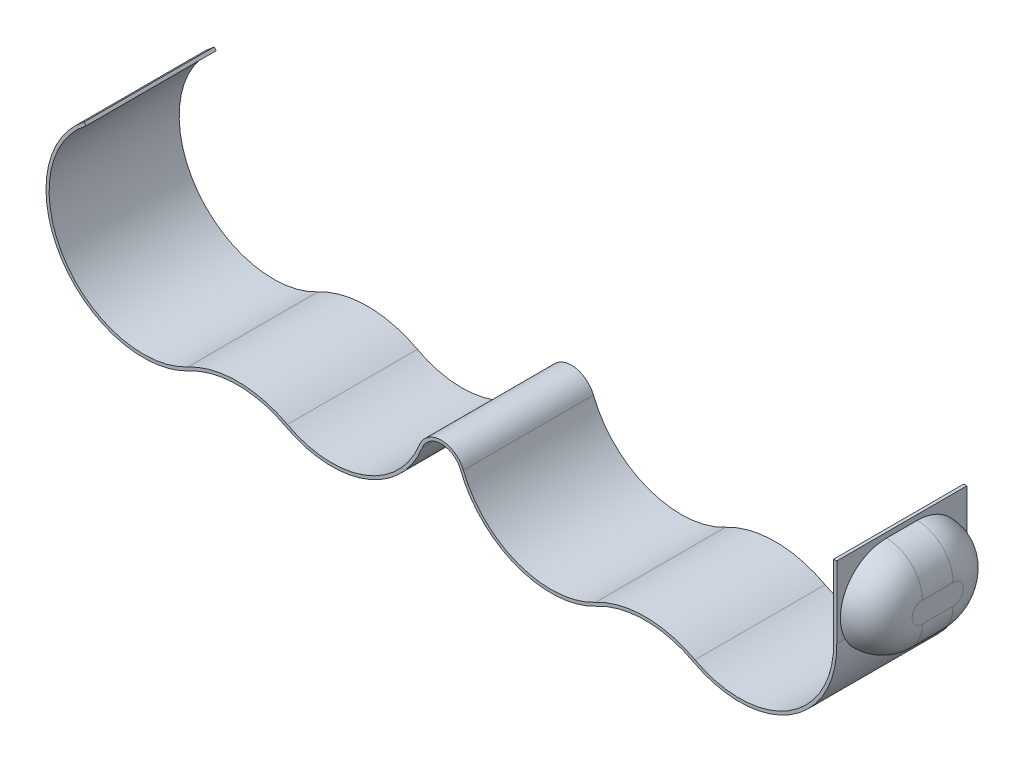
SolidWorks part; units mm, degrees
material "Kapton Film"
ref_plane "Front Plane" through (0, 0, 0) normal (0, 0, 1) x (1, 0, 0)
ref_plane "Top Plane" through (0, 0, 0) normal (0, 1, 0) x (1, 0, 0)
ref_plane "Right Plane" through (0, 0, 0) normal (1, 0, 0) x (0, 0, -1)
sketch "Battery Holder Outline" plane through (0, 0, 0) normal (0, 0, 1) x (1, 0, 0)
  line L0 (1.8682, 8) -> (-1.8682, 8) construction
  line L1 (-37.9318, 8) -> (-42.3, 8) construction
  line L2 (-42.3, 8) -> (-42.3, 0) construction
  line L3 (37.9318, 8) -> (42.3, 8) construction
  line L4 (42.3, 8) -> (42.3, 0) construction
  line L5 (42.3, 0) -> (-42.3, 0) construction
  arc A0 (-1.8682, 8) -> (-15.1821, 3.1238) centre (-10.7, 11.5) cw construction
  arc A1 (-24.6179, 3.1238) -> (-37.9318, 8) centre (-29.1, 11.5) cw construction
  arc A2 (24.6179, 3.1238) -> (37.9318, 8) centre (29.1, 11.5) ccw construction
  arc A3 (1.8682, 8) -> (15.1821, 3.1238) centre (10.7, 11.5) ccw construction
  arc A4 (24.6179, 3.1238) -> (15.1821, 3.1238) centre (19.9, -5.6933) ccw construction
  arc A5 (-15.1821, 3.1238) -> (-24.6179, 3.1238) centre (-19.9, -5.6933) ccw construction
  point P15 (0, 0)
  dimension "D1" = 9.5
  dimension "D2" = 10
  dimension "D3" = 84.6
  dimension "D4" = 8
  dimension "D5" = 3.7365
  dimension "D6" = 11.5
  dimension "D7" = 4.3682
sketch "Sketch2" plane through (0, 0, 0) normal (0, 0, 1) x (1, 0, 0)
  line L3 (-34.8747, 19.0434) -> (-34.6924, 18.8052)
  line L7 (38.5984, 11.6746) -> (38.5984, 18.6691)
  line L8 (38.5984, 18.6691) -> (38.2984, 18.6691)
  line L9 (38.2984, 18.6691) -> (38.2984, 11.6691)
  arc A0 (-15.1821, 3.1238) -> (-1.8682, 8) centre (-10.7, 11.5) ccw construction
  arc A1 (-15.1821, 3.1238) -> (-24.6179, 3.1238) centre (-19.9, -5.6933) ccw construction
  arc A2 (-37.9318, 8) -> (-24.6179, 3.1238) centre (-29.1, 11.5) ccw construction
  arc A3 (-15.1821, 3.1238) -> (-1.8682, 8) centre (-10.7, 11.5) ccw
  arc A4 (-15.1821, 3.1238) -> (-24.6179, 3.1238) centre (-19.9, -5.6933) ccw
  arc A5 (-37.9318, 8) -> (-24.6179, 3.1238) centre (-29.1, 11.5) ccw
  arc A13 (24.6179, 3.1238) -> (15.1821, 3.1238) centre (19.9, -5.6933) ccw construction
  arc A14 (1.8682, 8) -> (15.1821, 3.1238) centre (10.7, 11.5) ccw construction
  arc A15 (24.6179, 3.1238) -> (37.9318, 8) centre (29.1, 11.5) ccw construction
  arc A16 (24.6179, 3.1238) -> (38.5984, 11.6746) centre (29.1, 11.5) ccw
  arc A17 (24.6179, 3.1238) -> (15.1821, 3.1238) centre (19.9, -5.6933) ccw
  arc A18 (1.8682, 8) -> (15.1821, 3.1238) centre (10.7, 11.5) ccw
  arc A19 (-1.8682, 8) -> (1.8682, 8) centre (0, 7.2596) cw
  arc A21 (-37.9318, 8) -> (-34.8747, 19.0434) centre (-29.1, 11.5) cw
  arc A22 (-37.6529, 8.1105) -> (-34.6924, 18.8052) centre (-29.1, 11.5) cw
  arc A23 (-37.6529, 8.1105) -> (-24.7595, 3.3883) centre (-29.1, 11.5) ccw
  arc A24 (-15.0405, 3.3883) -> (-24.7595, 3.3883) centre (-19.9, -5.6933) ccw
  arc A25 (-15.0405, 3.3883) -> (-2.1471, 8.1105) centre (-10.7, 11.5) ccw
  arc A26 (-2.1471, 8.1105) -> (2.1471, 8.1105) centre (0, 7.2596) cw
  arc A27 (2.1471, 8.1105) -> (15.0405, 3.3883) centre (10.7, 11.5) ccw
  arc A28 (24.7595, 3.3883) -> (15.0405, 3.3883) centre (19.9, -5.6933) ccw
  arc A29 (24.7595, 3.3883) -> (38.2984, 11.6691) centre (29.1, 11.5) ccw
  arc A31 (38.5984, 11.6746) -> (37.4623, 16.008) centre (29.1, 11.5) ccw construction
  arc A32 (38.2984, 11.6691) -> (37.1982, 15.8656) centre (29.1, 11.5) ccw construction
  point P6 (37.9237, 15.0203)
  dimension "D1" = 0.3
  dimension "D4" = 7
  dimension "D2" = 19.1406
  dimension "D3" = 12.3
extrude "Boss-Extrude1" add sketch "Sketch2" along normal mid plane 12.7
ref_plane "Plane1" through (37.9237, 15.0203, 0) normal (0.9288, 0.3706, 0) x (0, 0, -1)
ref_plane "Plane2" through (42.5677, 16.8731, 0) normal (0.9288, 0.3706, 0) x (0, 0, -1)
sketch "Sketch6" plane through (38.5984, 16.1106, 0) normal (1, 0, 0) x (0, 0, -1)
  line L0 (-1.5, -2.4415) -> (1.5, -2.4415) construction
  line L1 (-1.5, 2.0585) -> (1.5, 2.0585)
  line L2 (-1.5, -6.9415) -> (1.5, -6.9415)
  line L3 (-6.35, 2.5585) -> (6.35, 2.5585) construction
  arc A0 (-1.5, 2.0585) -> (-1.5, -6.9415) centre (-1.5, -2.4415) ccw
  arc A1 (1.5, -6.9415) -> (1.5, 2.0585) centre (1.5, -2.4415) ccw
  point P2 (0, -2.4415)
  point P12 (0, 2.5585)
  point P14 (6, -2.4415)
  point P15 (-6, -2.4415)
  dimension "D1" = 12
  dimension "D3" = 0.5
  dimension "D2" = 9
extrude "Boss-Extrude3" add sketch "Sketch6" against normal up to next (0.2999 mm away) and the other way blind 3.51
sketch "Sketch5" plane through (0, 0, 6.35) normal (0, 0, 1) x (1, 0, 0)
  line L2 (36.9572, 21.8694) -> (47.6324, 21.8694)
  line L3 (47.6324, 21.8694) -> (47.6324, 11.5)
  line L4 (47.6324, 11.5) -> (42.11, 11.5)
  line L5 (38.5984, 18.1691) -> (42.1084, 18.1691) construction
  arc A0 (24.7595, 3.3883) -> (38.2984, 11.6691) centre (29.1, 11.5) ccw construction
  arc A1 (36.9572, 21.8694) -> (42.11, 11.5) centre (29.1, 11.5) cw
  dimension "D1" = 13.01
  dimension "D3" = 12
  dimension "D2" = 5.5224
extrude "Cut-Extrude1" [suppressed] cut sketch "Sketch5" against normal through all
fillet "Fillet1" [suppressed] radius 3.5 type face fillet
fillet "Fillet2" radius 3.5 4 edges at (42.1084, 18.1691, 0) (42.1084, 13.6691, -6) (42.1084, 9.1691, 0) (42.1084, 13.6691, 6)
